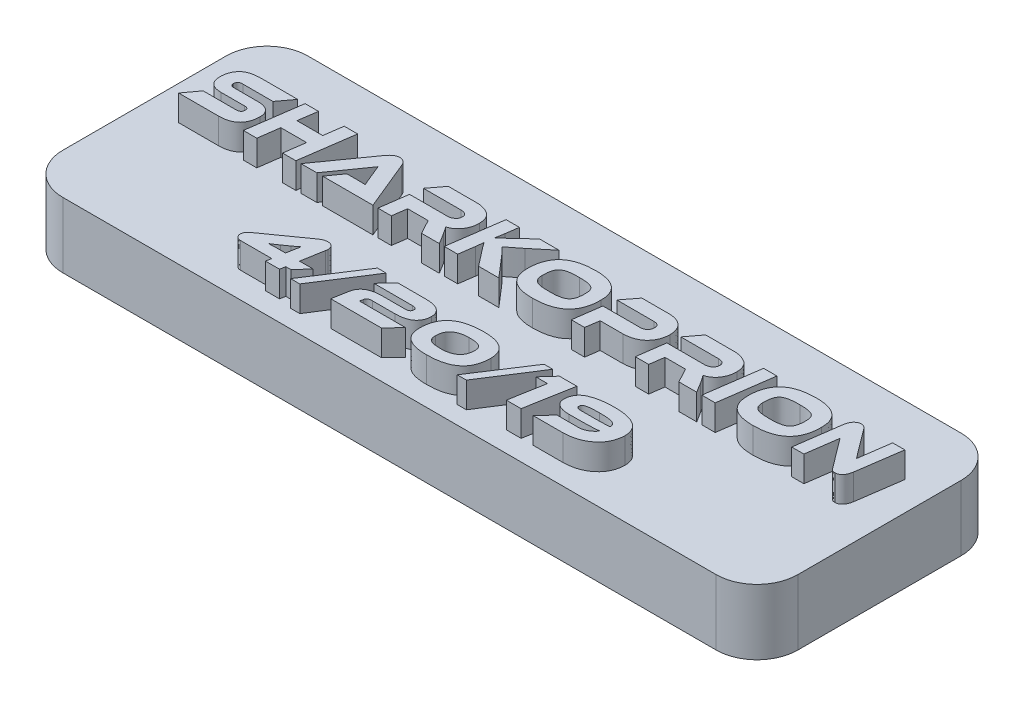
SolidWorks part; units mm, degrees
ref_plane "Front Plane" through (0, 0, 0) normal (0, 0, 1) x (1, 0, 0)
ref_plane "Top Plane" through (0, 0, 0) normal (0, 1, 0) x (1, 0, 0)
ref_plane "Right Plane" through (0, 0, 0) normal (1, 0, 0) x (0, 0, -1)
sketch "Sketch1" plane through (0, 0, 0) normal (0, 1, 0) x (1, 0, 0)
  line L1 (-28.575, 9.525) -> (28.575, 9.525)
  line L2 (-28.575, 9.525) -> (-28.575, -9.525)
  line L3 (-28.575, -9.525) -> (28.575, -9.525)
  line L4 (28.575, 9.525) -> (28.575, -9.525)
  line L5 (-28.575, 9.525) -> (28.575, -9.525) construction
  line L6 (-28.575, -9.525) -> (28.575, 9.525) construction
  point P0 (0, 0)
  dimension "D1" = 57.15
  dimension "D2" = 19.05
extrude "Boss-Extrude1" add sketch "Sketch1" along normal up to surface (5.08 mm away)
fillet "Fillet1" radius 3.175 4 edges at (-28.575, 2.54, 9.525) (-28.575, 2.54, -9.525) (28.575, 2.54, 9.525) (28.575, 2.54, -9.525)
sketch "Sketch3" plane through (0, 5.08, 0) normal (0, 1, 0) x (1, 0, 0)
  line L0 (28.575, -7.9375) -> (-28.575, -7.9375) construction
  line L1 (28.575, -6.35) -> (28.575, 6.35) construction
  line L2 (-28.575, 6.35) -> (-28.575, -6.35) construction
  line L3 (28.575, 0) -> (-28.575, 0) construction
  line L5 (-25.4, -9.525) -> (25.4, -9.525) construction
  line L6 (25.4, 9.525) -> (-25.4, 9.525) construction
  text T0 "SharkoprioN\r\n\r\n" font "Ethnocentric Rg" height in points 16
  text T1 "4/20/19" font "Ethnocentric Rg" height in points 14
  point P8 (-28.575, 0)
  dimension "D1" = 1.5875
extrude "Boss-Extrude2" add sketch "Sketch3" along normal blind 2
sketch "Sketch4" plane through (0, 0, 0) normal (0, -1, 0) x (1, 0, 0)
  line L0 (25.4, 0) -> (-25.4, 0) construction
  circle A0 centre (-25.4, 0) radius 0.9
  circle A1 centre (25.4, 0) radius 0.9
  point P3 (0, 0)
  dimension "D2" = 1.8
  dimension "D1" = 50.8
extrude "Cut-Extrude1" cut sketch "Sketch4" against normal blind 4
